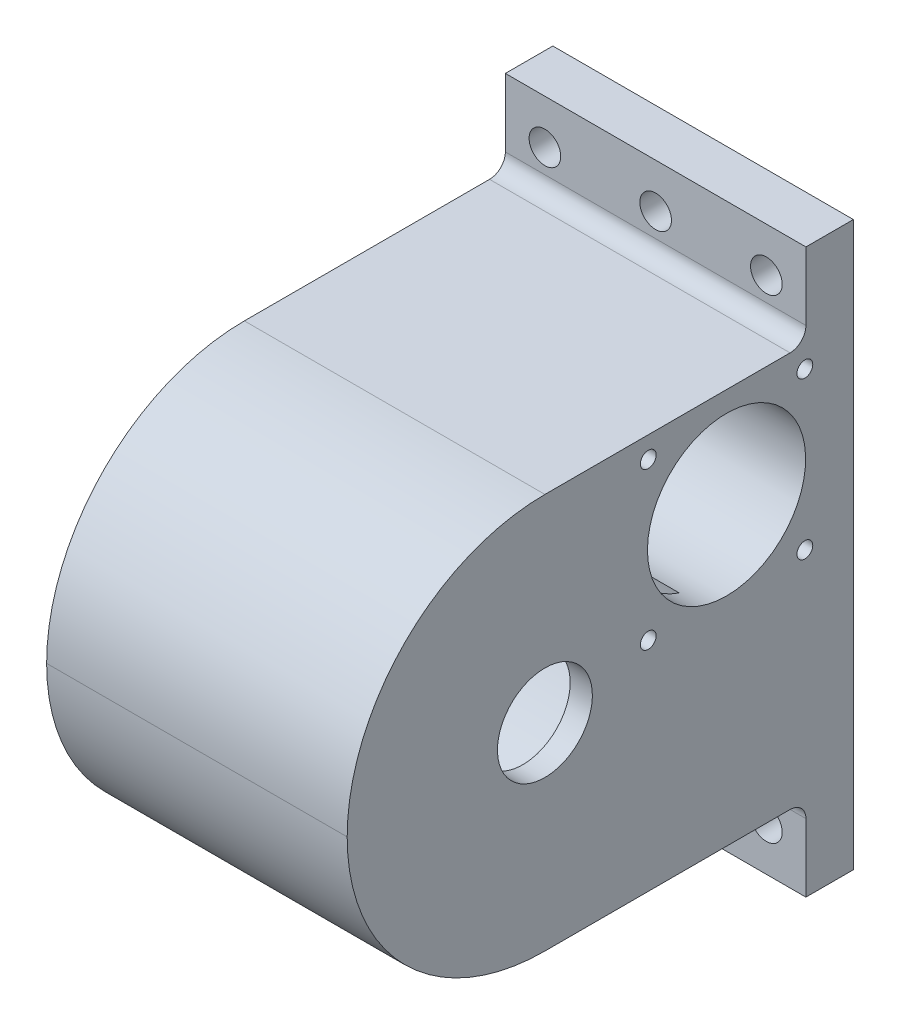
SolidWorks part; units mm, degrees
ref_plane "前视基准面" through (0, 0, 0) normal (0, 0, 1) x (1, 0, 0)
ref_plane "上视基准面" through (0, 0, 0) normal (0, 1, 0) x (1, 0, 0)
ref_plane "右视基准面" through (0, 0, 0) normal (1, 0, 0) x (0, 0, -1)
sketch "草图1" plane through (0, 0, 0) normal (0, 0, 1) x (1, 0, 0)
  line L1 (0, 0) -> (95, 0)
  line L2 (0, 0) -> (0, -178)
  line L3 (0, -178) -> (95, -178)
  line L4 (95, 0) -> (95, -178)
  dimension "D1" = 178
  dimension "D2" = 95
extrude "拉伸1" add sketch "草图1" along normal blind 160
sketch "草图2" plane through (95, 0, 0) normal (1, 0, 0) x (0, 0, -1)
  line L0 (0, -178) -> (0, 0) construction
  line L1 (-160, -178) -> (-15, -178)
  line L2 (-160, -178) -> (-160, -151.5)
  line L3 (-160, -151.5) -> (-15, -151.5)
  line L4 (-15, -178) -> (-15, -151.5)
  line L7 (-15, 0) -> (-15, -26.5)
  line L8 (-200, -26.5) -> (-15, -26.5)
  line L9 (-200, 0) -> (-200, -26.5)
  line L10 (-200, 0) -> (-15, 0)
  dimension "D1" = 15
extrude "切除-拉伸1" cut sketch "草图2" against normal through all
fillet "圆角1" radius 62.5 2 edges at (47.5, -26.5, 160) (47.5, -151.5, 160)
sketch "草图3" plane through (95, 0, 0) normal (1, 0, 0) x (0, 0, -1)
  circle A0 centre (-97.5, -89) radius 50
  dimension "D1" = 100
extrude "切除-拉伸2" cut sketch "草图3" against normal blind 230
sketch "草图5" plane through (95, 0, 0) normal (1, 0, 0) x (0, 0, -1)
  circle A0 centre (-97.5, -89) radius 50
  circle A1 centre (-97.5, -89) radius 15
  dimension "D1" = 30
  dimension "D2" = 100
extrude "拉伸3" add sketch "草图5" against normal blind 7
sketch "草图6" plane through (95, 0, 0) normal (1, 0, 0) x (0, 0, -1)
  circle A3 centre (-40.0843, -58) radius 25
extrude "切除-拉伸3" cut sketch "草图6" against normal blind 40
sketch "草图11" plane through (95, 0, 0) normal (1, 0, 0) x (0, 0, -1)
  circle A0 centre (-64.833, -82.7487) radius 2.5
  circle A5 centre (-64.833, -33.2513) radius 2.5
  circle A6 centre (-15.3356, -33.2513) radius 2.5
  circle A7 centre (-15.3356, -82.7487) radius 2.5
extrude "切除-拉伸4" cut sketch "草图11" against normal blind 15
sketch "草图12" plane through (0, 0, 0) normal (0, 0, -1) x (-1, 0, 0)
  line L0 (-45, -39) -> (-20, -39)
  line L1 (-75, -89) -> (-75, -139)
  line L3 (-45, -139) -> (-20, -139)
  line L4 (-20, -39) -> (-20, -139)
  line L7 (0, 0) -> (0, -178) construction
  line L10 (-45, -39) -> (-45, -89)
  line L11 (-45, -89) -> (-75, -89)
  line L12 (-75, -139) -> (-45, -139)
  dimension "D4" = 20
extrude "切除-拉伸5" cut sketch "草图12" against normal blind 40
sketch "草图13" plane through (0, 0, 0) normal (-1, 0, 0) x (0, 0, 1)
  circle A1 centre (153.5, -89) radius 3
  circle A2 centre (142.805, -121.916) radius 3
  circle A3 centre (114.805, -142.2592) radius 3
  circle A4 centre (80.195, -142.2592) radius 3
  circle A5 centre (52.195, -121.916) radius 3
  circle A6 centre (41.5, -89) radius 3
  circle A7 centre (52.195, -56.084) radius 3
  circle A8 centre (80.195, -35.7408) radius 3
  circle A9 centre (114.805, -35.7408) radius 3
  circle A10 centre (142.805, -56.084) radius 3
extrude "切除-拉伸6" cut sketch "草图13" against normal blind 20
sketch "草图14" plane through (0, 0, 15) normal (0, 0, 1) x (1, 0, 0)
  line L13 (12.5, -164) -> (47.5, -164) construction
  circle A0 centre (12.5, -164) radius 5
  circle A1 centre (47.5, -164) radius 5
  circle A2 centre (82.5, -164) radius 5
  circle A3 centre (12.5, -14) radius 5
  circle A4 centre (47.5, -14) radius 5
  circle A5 centre (82.5, -14) radius 5
extrude "切除-拉伸7" cut sketch "草图14" against normal blind 40
fillet "圆角2" radius 5 2 edges at (47.5, -26.5, 15) (47.5, -151.5, 15)
